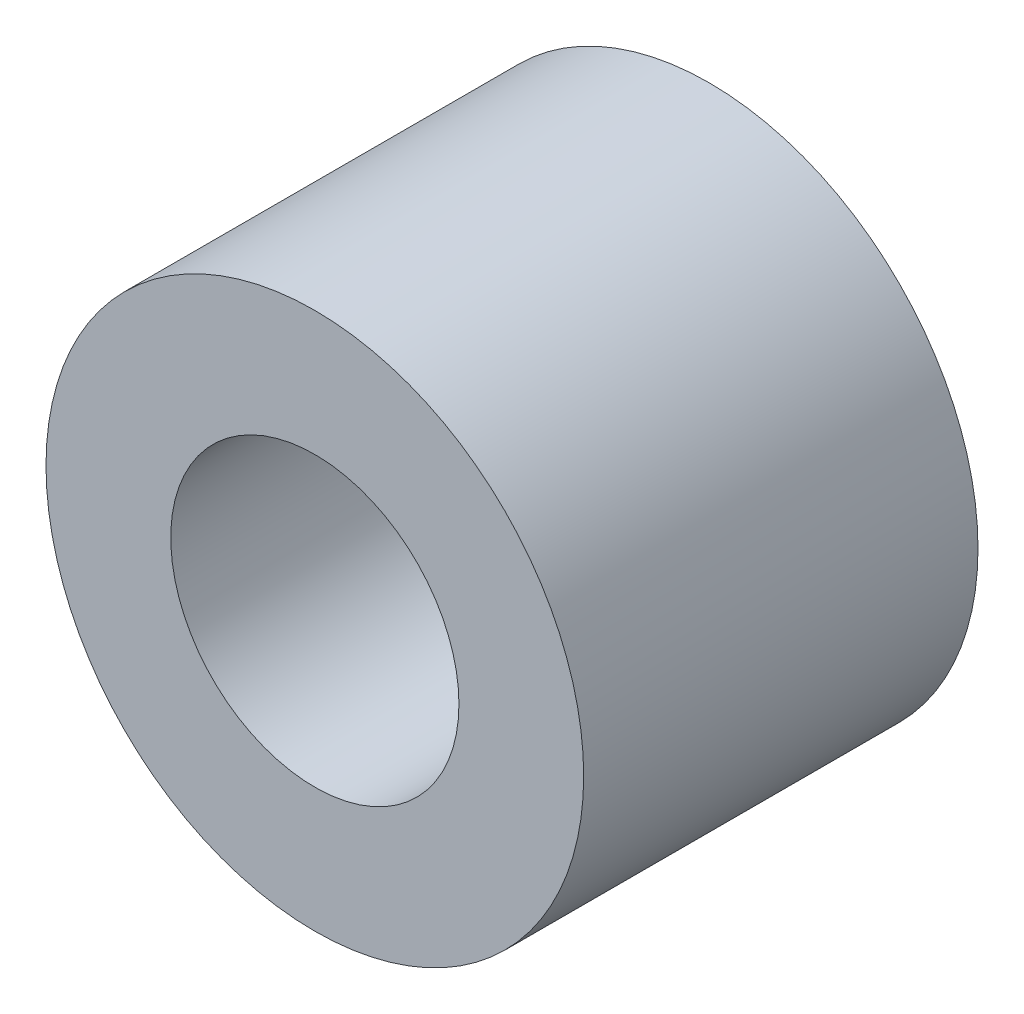
SolidWorks part; units mm, degrees
material "6061-T6 (SS)"
ref_plane "Front Plane" through (0, 0, 0) normal (0, 0, 1) x (1, 0, 0)
ref_plane "Top Plane" through (0, 0, 0) normal (0, 1, 0) x (1, 0, 0)
ref_plane "Right Plane" through (0, 0, 0) normal (1, 0, 0) x (0, 0, -1)
sketch "Sketch1" plane through (0, 0, 0) normal (0, 0, 1) x (1, 0, 0)
  circle A0 centre (0, 0) radius 2.5527
  circle A1 centre (0, 0) radius 4.7625
  dimension "D1" = 5.1054
  dimension "D2" = 9.525
extrude "Boss-Extrude1" add sketch "Sketch1" along normal mid plane 6.985
